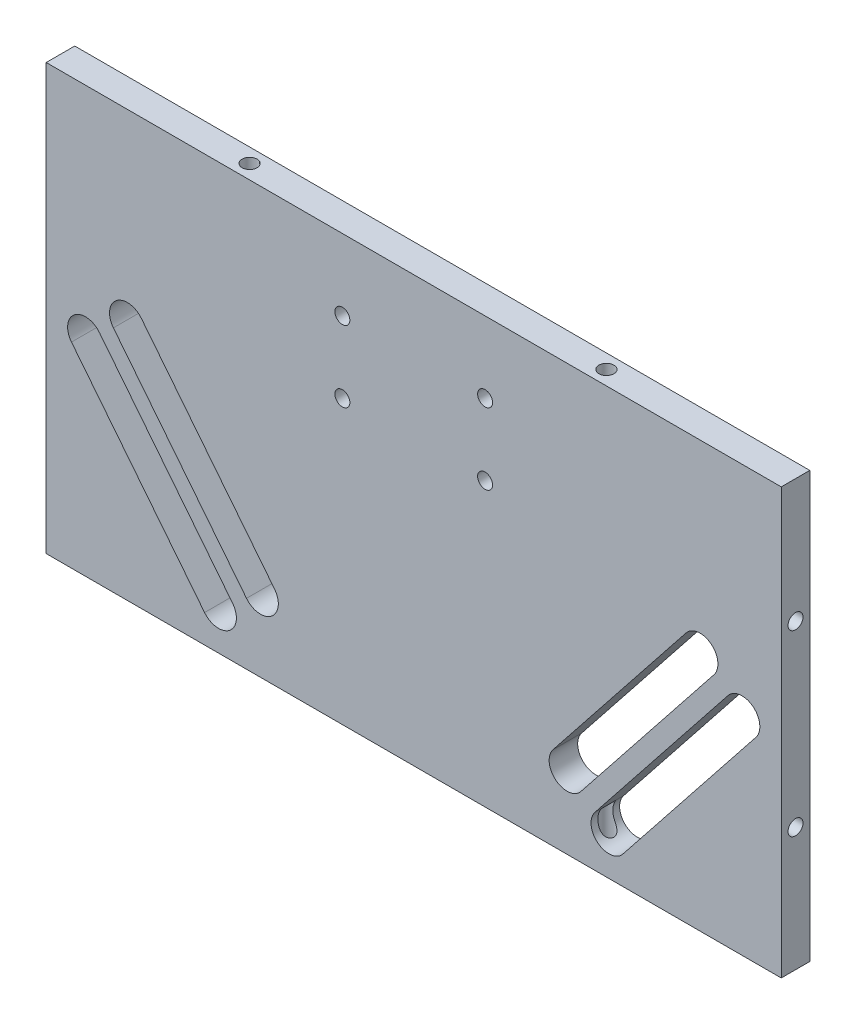
SolidWorks part; units mm, degrees
ref_plane "Front Plane" through (0, 0, 0) normal (1, 0, 0) x (0, 1, 0)
ref_plane "Top Plane" through (0, 0, 0) normal (0, 0, 1) x (0, 1, 0)
ref_plane "Right Plane" through (0, 0, 0) normal (0, 1, 0) x (-1, 0, 0)
sketch "Sketch1" plane through (0, 0, 0) normal (0, 0, 1) x (0, 1, 0)
  line L0 (11, 157.6975) -> (57.9949, 195) construction
  line L1 (0, 0) -> (119.2019, 0)
  line L2 (0, 0) -> (0, 206)
  line L3 (0, 206) -> (119.2019, 206)
  line L4 (119.2019, 0) -> (119.2019, 206)
  line L5 (7.8915, 161.6138) -> (54.8864, 198.9162)
  line L6 (14.1085, 153.7813) -> (61.1035, 191.0838)
  line L7 (20.3256, 145.9488) -> (67.3206, 183.2513) construction
  line L8 (17.2171, 149.865) -> (64.212, 187.1675)
  line L9 (23.4342, 142.0325) -> (70.4291, 179.335)
  line L10 (20.3256, 60.0512) -> (67.3206, 22.7487) construction
  line L11 (23.4342, 63.9675) -> (70.4291, 26.665)
  line L12 (17.2171, 56.135) -> (64.212, 18.8325)
  line L13 (11, 48.3025) -> (57.9949, 11) construction
  line L14 (14.1085, 52.2187) -> (61.1035, 14.9162)
  line L15 (7.8915, 44.3862) -> (54.8864, 7.0838)
  line L16 (6, 200) -> (113.2019, 200) construction
  line L17 (113.2019, 6) -> (113.2019, 200) construction
  line L18 (6, 6) -> (113.2019, 6) construction
  line L19 (6, 6) -> (6, 200) construction
  line L20 (56.238, 148.9593) -> (79.2755, 119.9359) construction
  line L21 (68.9422, 73.0459) -> (50.0586, 49.2557) construction
  line L22 (119.2019, 103) -> (0, 103) construction
  arc A0 (7.8915, 161.6138) -> (14.1085, 153.7813) centre (11, 157.6975) ccw
  arc A1 (61.1035, 191.0838) -> (54.8864, 198.9162) centre (57.9949, 195) ccw
  arc A2 (17.2171, 149.865) -> (23.4342, 142.0325) centre (20.3256, 145.9488) ccw
  arc A3 (70.4291, 179.335) -> (64.212, 187.1675) centre (67.3206, 183.2513) ccw
  arc A4 (23.4342, 63.9675) -> (17.2171, 56.135) centre (20.3256, 60.0512) ccw
  arc A5 (64.212, 18.8325) -> (70.4291, 26.665) centre (67.3206, 22.7487) ccw
  arc A6 (14.1085, 52.2187) -> (7.8915, 44.3862) centre (11, 48.3025) ccw
  arc A7 (54.8864, 7.0838) -> (61.1035, 14.9162) centre (57.9949, 11) ccw
  circle A8 centre (79.2019, 123) radius 2.1
  circle A9 centre (99.2019, 123) radius 2.1
  circle A10 centre (79.2019, 83) radius 2.1
  circle A11 centre (99.2019, 83) radius 2.1
  point P7 (34.4975, 176.3488)
  point P12 (43.8231, 164.6)
  point P19 (43.8231, 41.4)
  point P26 (34.4975, 29.6512)
  point P40 (92.7184, 103)
  dimension "D9" = 4.2
  dimension "D1" = 119.2019
  dimension "D2" = 206
  dimension "D4" = 5
  dimension "D5" = 5
  dimension "D6" = 103.118
  dimension "D7" = 10
  dimension "D8" = 60
  dimension "D10" = 20
  dimension "D11" = 20
  dimension "D12" = 20
  dimension "D3" = 6
extrude "Boss-Extrude1" add sketch "Sketch1" along normal blind 8
sketch "Sketch2" plane through (0, 0, 0) normal (0, -1, 0) x (1, 0, 0)
  line L2 (-206, 4) -> (0, 4) construction
  line L3 (-206, 8) -> (-206, 0) construction
  line L4 (0, 8) -> (0, 0) construction
  line L5 (-103, 8) -> (-103, 0) construction
  line L6 (-206, 8) -> (0, 8) construction
  line L7 (-206, 0) -> (0, 0) construction
  circle A0 centre (-153, 4) radius 2.1
  circle A1 centre (-53, 4) radius 2.1
  dimension "D1" = 4.2
  dimension "D2" = 50
extrude "Cut-Extrude1" cut sketch "Sketch2" against normal blind 14
extrude "Cut-Extrude2" cut sketch "Sketch2<2>" along normal blind 14 from surface starting at face at (-103, 119.2019, 4)
sketch "Sketch2<2>" plane through (0, 0, 0) normal (0, -1, 0) x (1, 0, 0) same geometry as "Sketch2"
sketch "Sketch3" plane through (0, 0, 0) normal (1, 0, 0) x (0, 1, 0)
  line L0 (105.2019, 4) -> (119.2019, 4) construction
  line L1 (0, 4) -> (119.2019, 4) construction
  line L2 (0, 8) -> (0, 0) construction
  line L3 (119.2019, 8) -> (119.2019, 0) construction
  line L4 (0, 8) -> (119.2019, 8) construction
  line L5 (59.6009, 8) -> (59.6009, 0) construction
  line L6 (0, 0) -> (119.2019, 0) construction
  circle A0 centre (34.6009, 4) radius 2.1
  circle A1 centre (84.601, 4) radius 2.1
  dimension "D1" = 4.2
  dimension "D2" = 50
extrude "Cut-Extrude3" cut sketch "Sketch3" against normal blind 14
extrude "Cut-Extrude4" cut sketch "Sketch3<2>" along normal blind 14 from surface starting at face at (-206, 59.6009, 4)
sketch "Sketch3<2>" plane through (0, 0, 0) normal (1, 0, 0) x (0, 1, 0) same geometry as "Sketch3"
sketch "Sketch4" plane through (0, 0, 8) normal (0, 0, 1) x (1, 0, 0)
  line L0 (0, 0) -> (0, 119.2019) construction
  line L1 (-206, 0) -> (0, 0) construction
  line L2 (0, 119.2019) -> (-206, 119.2019) construction
  line L3 (-206, 119.2019) -> (-206, 0) construction
  line L4 (0, 0) -> (0, 119.2019)
  line L5 (-206, 0) -> (0, 0)
  line L6 (0, 119.2019) -> (-206, 119.2019)
  line L7 (-206, 119.2019) -> (-206, 0)
equation "\"MotorDriverLength\"= 60mm"
equation "\"MotorLength\"= 60"
equation "\"MotorDriverWidth\"=44"
equation "\"MotorWidth\"= 37"
equation "\"InnerWallThickness\"=3"
equation "\"BatteryWidth\"= 60"
equation "\"OuterWallThickness\" = 8"
equation "\"CompartmentHeight\"=37"
equation "\"CompartmentWidth\"= \"MotorDriverLength\""
equation "\"MotorDiameter\"=37"
equation "\"BatteryHeight\"=24.2019"
equation "\"MotorDriverHeight\"=28"
equation "\"CircuitHeight\"=30"
equation "\"FanThickness\"= 10"
equation "\"FanHeight\"=50"
equation "\"MotorShaftHole\"=12"
equation "\"BearingBore\"=4"
equation "\"MinShinWidth\"= 20"
equation "\"ShinThickness\"=10"
equation "\"PivotDistance\"=30"
equation "\"ThighLength\"= 200"
equation "\"KneeLength\" =20"
equation "\"HipBore\"=27"
equation "\"ThighThickness\"=20"
equation "\"MaxBending\"=135"
equation "\"MaxStretchingAngle\"= 140"
equation "\"ThighJointDistance\"=157.485"
equation "\"ShinLength\"=120"
equation "\"BearingDiameter\"= 10"
equation "\"CircuitLength\"=50"
equation "\"ChessisInnerWidth\"= \"OuterWallThickness\" * 2 + \"MotorDriverLength\" + \"MotorDiameter\" + \"InnerWallThickness\" * 3 + \"CircuitLength\""
equation "\"ChessisHeight\"= \"BatteryHeight\" + 10 + \"InnerWallThickness\" + \"MotorDriverHeight\"*2 + 10 + \"OuterWallThickness\" * 2"
equation "\"D1@Sketch1\"=\"ChessisHeight\""
equation "\"ChassisWidth\"= \"MotorDriverWidth\"*4+30"
equation "\"D2@Sketch1\"=\"ChassisWidth\""
equation "\"D1@Boss-Extrude1\"=\"OuterWallThickness\""
